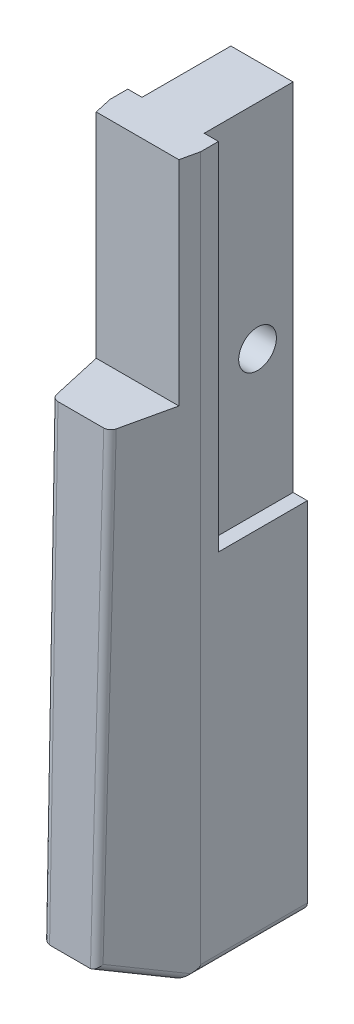
SolidWorks part; units mm, degrees
ref_plane "Front Plane" through (0, 0, 0) normal (1, 0, 0) x (0, 1, 0)
ref_plane "Top Plane" through (0, 0, 0) normal (0, 0, 1) x (0, 1, 0)
ref_plane "Right Plane" through (0, 0, 0) normal (0, 1, 0) x (-1, 0, 0)
sketch "Sketch1" plane through (0, 0, 0) normal (0, 0, 1) x (0, 1, 0)
  line L1 (0, 0) -> (100, 0)
  line L2 (0, 0) -> (0, 11.75)
  line L3 (0, 11.75) -> (100, 11.75)
  line L4 (100, 0) -> (100, 11.75)
  dimension "D1" = 100
  dimension "D2" = 11.75
extrude "Boss-Extrude1" add sketch "Sketch1" along normal blind 17.5
sketch "Sketch5" plane through (0, 0, 0) normal (1, 0, 0) x (0, 1, 0)
  line L1 (100, 17.5) -> (70, 17.5)
  line L2 (100, 17.5) -> (100, 5)
  line L3 (100, 5) -> (70, 5)
  line L4 (70, 17.5) -> (70, 5)
  circle A0 centre (70, 5) radius 2.65
  dimension "D1" = 30
extrude "Cut-Extrude2" cut sketch "Sketch5" against normal through all contours A0
sketch "Sketch4" plane through (0, 0, 0) normal (1, 0, 0) x (0, 1, 0)
  line L0 (100, 17.5) -> (100, 12.5)
  line L1 (100, 17.5) -> (100, 0) construction
  line L3 (100, 12.5) -> (50, 12.5)
  line L4 (100, 12.5) -> (100, 0)
  line L5 (100, 0) -> (50, 0)
  line L6 (50, 12.5) -> (50, 0)
  line M6 (0, 0) -> (100, 0)
  line M7 (100, 0) -> (100, 17.5)
  circle M10 centre (70, 5) radius 2.65
  dimension "D1" = 50
  dimension "D2" = 12.5
extrude "Cut-Extrude3" cut sketch "Sketch4" against normal blind 1.5 contours L3 L6 M6 M7 M10 region at (0, 75.183, 6.2957)
ref_plane "Plane1" through (-5.875, 0, 0) normal (1, 0, 0) x (0, 0, -1)
mirror "Mirror1" about plane through (-5.875, 0, 0) normal (1, 0, 0) of "Cut-Extrude3"
sketch "Sketch9" plane through (0, 0, 0) normal (1, 0, 0) x (0, 1, 0)
  line L1 (0, 17.5) -> (50, 17.5)
  line L2 (0, 17.5) -> (0, 0)
  line L3 (0, 0) -> (50, 0)
  line L4 (50, 12.5) -> (50, 0)
  line L5 (50, 17.5) -> (100, 17.5)
  line L7 (50, 12.5) -> (100, 12.5)
  line L8 (100, 17.5) -> (100, 12.5)
extrude "Boss-Extrude3" add sketch "Sketch9" along normal blind 0.5
mirror "Mirror4" about plane through (-5.875, 0, 0) normal (1, 0, 0) of "Boss-Extrude3"
sketch "Sketch6" plane through (0.5, 0, 0) normal (1, 0, 0) x (0, 1, 0)
  line L0 (0, 17.5) -> (4.75, 27)
  line L1 (4.75, 27) -> (90, 25)
  line L2 (90, 25) -> (100, 17.5)
  line L4 (70, 5) -> (70, 12.5) construction
  line L5 (70, 12.5) -> (70, 25.4692)
  line L6 (0, 17.5) -> (0, 0)
  line L7 (0, 0) -> (50, 0)
  line L8 (50, 0) -> (50, 12.5)
  line L9 (50, 12.5) -> (100, 12.5)
  line L12 (100, 12.5) -> (100, 17.5)
extrude "Boss-Extrude2" add sketch "Sketch6" against normal blind 12.75
sketch "Sketch7" plane through (0, 100, 0) normal (0, 1, 0) x (-1, 0, 0)
  line L0 (-0.5, 15) -> (12.25, 15) construction
  line L1 (1.5, 0) -> (10.25, 0) construction
  line L2 (1.5, 0) -> (1.5, 17.5) construction
  line L3 (1.5, 17.5) -> (10.25, 17.5) construction
  line L4 (10.25, 0) -> (10.25, 17.5) construction
  line L7 (-0.5, 15) -> (2.202, 27)
  line L8 (12.25, 27) -> (-0.5, 27) construction
  line L9 (12.25, 12.5) -> (12.25, 17.5) construction
  line L10 (-0.5, 12.5) -> (-0.5, 17.5) construction
  line L11 (-0.5, 17.5) -> (-0.5, 15) construction
  line L12 (12.25, 17.5) -> (12.25, 15) construction
extrude "Cut-Extrude4" cut sketch "Sketch7" against normal through all and the other way through all
mirror "Mirror3" about plane through (-5.875, 0, 0) normal (1, 0, 0) of "Cut-Extrude4"
fillet "Fillet4" radius 1 5 edges at (-10.6175, 2.375, 22.25) (-5.875, 0, 17.5) (-1.1325, 2.375, 22.25) (-2.0297, 37.375, 26.2346) (-9.7203, 37.375, 26.2346)
fillet "Fillet3" radius 1 2 edges at (-12.25, 0, 7.5) (0.5, 0, 7.5)
equation "\"whitekey_cutout_length\"= 101.5"
equation "\"mount_recess_length\"=50"
equation "\"mount_recess_height\"=12.5"
equation "\"mount_recess_depth\"=1.5"
equation "\"D1@Sketch4\"=\"mount_recess_length\""
equation "\"D2@Sketch4\"=\"mount_recess_height\""
equation "\"D1@Cut-Extrude3\"=\"mount_recess_depth\""
equation "\"D1@Sketch5\"=\"mount_recess_length\"-20"
equation "\"D1@Sketch1\"=\"whitekey_cutout_length\"-1.5"
